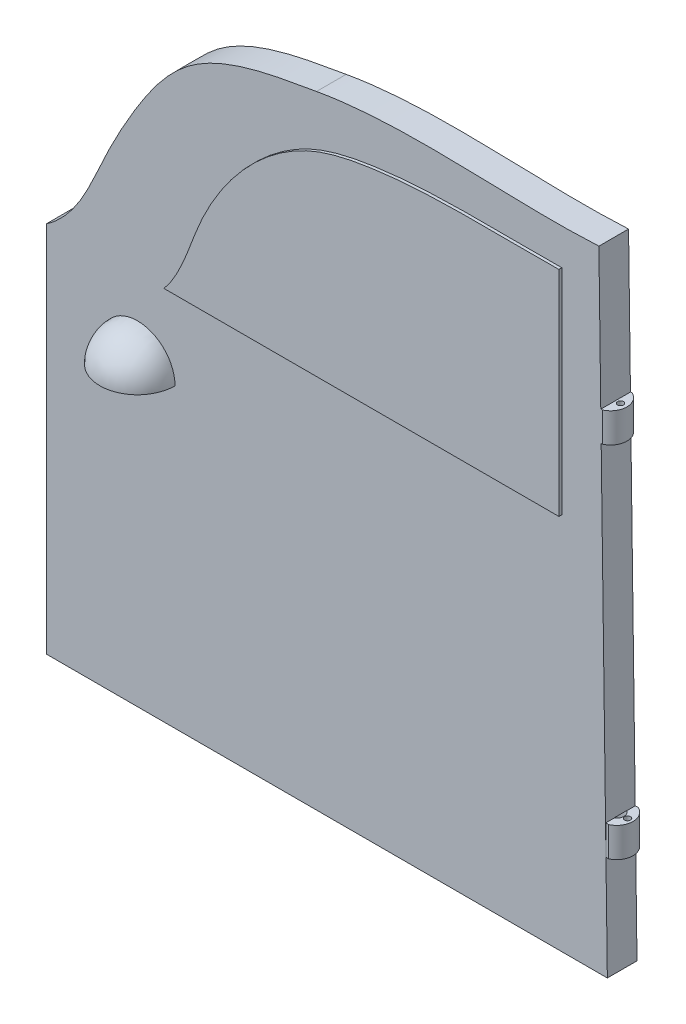
SolidWorks part; units mm, degrees
ref_plane "Front Plane" through (0, 0, 0) normal (0, 0, 1) x (1, 0, 0)
ref_plane "Top Plane" through (0, 0, 0) normal (0, 1, 0) x (1, 0, 0)
ref_plane "Right Plane" through (0, 0, 0) normal (1, 0, 0) x (0, 0, -1)
sketch "Sketch1" plane through (0, 0, 0) normal (0, 0, 1) x (1, 0, 0)
  line L0 (-221.4454, 149.8652) -> (535.2213, 149.8652) construction
  line L1 (186.2801, 212.2169) -> (189.1274, 0)
  line L2 (189.1274, 0) -> (0, 0)
  line L3 (0, 0) -> (0, 125.5767)
  spline S0 degree 3 poles (0, 125.5767) (10.557, 132.8376) (17.0982, 150.7511) (30.5385, 175.7634) (49.3522, 203.0408) (76.8679, 207.297) (91.098, 209.7763) knots 0 0 0 0 0.275246 0.426572 0.655829 1 1 1 1
  spline S1 degree 3 poles (91.098, 209.7763) (122.5651, 215.3748) (154.601, 210.5155) (186.2801, 212.2169) knots 0 0 0 0 1 1 1 1
sketch "Sketch2" plane through (0, 0, 0) normal (0, 0, 1) x (1, 0, 0)
extrude "Boss-Extrude1" add sketch "Sketch1" along normal blind 10
sketch "Sketch3" plane through (0, 0, 10) normal (0, 0, 1) x (1, 0, 0)
  line L0 (40.6919, 127.5652) -> (173.8037, 127.5652)
  line L1 (173.8037, 127.5652) -> (173.8037, 199.6793)
  spline S0 degree 3 poles (40.6919, 127.5652) (46.7713, 134.9333) (53.3691, 161.7045) (78.4575, 191.2123) (124.3175, 201.0388) (152.2649, 199.3628) (173.8037, 199.6793) knots 0 0 0 0 0.165618 0.500502 0.611599 1 1 1 1
extrude "Boss-Extrude2" add sketch "Sketch3" along normal blind 1 and the other way blind 11
sketch "Sketch4" plane through (0, 0, 10) normal (0, 0, 1) x (1, 0, 0)
  line L0 (18.099, 100.0012) -> (43.4131, 100.0012)
  line L1 (30.756, 100.0012) -> (30.756, 0) construction
  line L2 (0, 0) -> (189.1274, 0) construction
  line L3 (30.756, 100.0012) -> (187.7857, 100.0012) construction
  line L4 (189.1274, 0) -> (186.2801, 212.2169) construction
  arc A0 (18.099, 100.0012) -> (43.4131, 100.0012) centre (30.756, 100.0012) cw
  dimension "D1" = 100.0012
ref_plane "Plane1" through (0, 100, 0) normal (0, -1, 0) x (-1, 0, 0)
sketch "Sketch5" plane through (0, 100, 0) normal (0, -1, 0) x (-1, 0, 0)
  line L0 (-18.099, -10) -> (-43.4131, -10)
  line L1 (-18.099, -10) -> (-43.4131, -10) construction
  line L2 (0, -10) -> (-189.1274, -10) construction
  line L3 (-43.4131, -10) -> (-18.099, -10) construction
  arc A0 (-18.099, -10) -> (-43.4131, -10) centre (-30.756, -5.6887) cw
ref_plane "Plane2" through (32.1075, 0.4308, 0) normal (0.9999, 0.0134, 0) x (0, 0, -1)
sketch "Sketch6" plane through (32.1075, 0.4308, 0) normal (0.9999, 0.0134, 0) x (0, 0, -1)
  line L1 (-10, 112.2366) -> (-10, 99.4097) construction
  ellipse E3 centre (-5.6887, 99.5784) end of major axis (-19.0599, 99.5784) minor radius 0.1794 (-10, 99.7482) -> (-10, 99.4086) ccw construction
  spline S0 degree 3 poles (-19.0598, 99.5782) (-18.7168, 104.9477) (-15.4228, 110.6613) (-10, 112.2366) knots 0 0 0 0 1 1 1 1
revolve "Revolve1" add sketch "Sketch4" angle 90 about L0
sketch "Sketch7" plane through (0, 100.0012, 0) normal (0, -1, 0) x (1, 0, 0)
  line L0 (18.099, 10) -> (43.4131, 10) construction
  line L1 (19.7854, 10) -> (41.9159, 10) construction
  line L2 (19.7854, 10) -> (41.9159, 10)
  arc A0 (19.7854, 10) -> (41.9159, 10) centre (30.8507, 8.9637) cw
revolve "Cut-Revolve1" cut sketch "Sketch7" angle 45 about L1 other way angle 90
ref_plane "Plane3" through (0, 40, 0) normal (0, -1, 0) x (-1, 0, 0)
ref_plane "Plane4" through (0, 160, 0) normal (0, -1, 0) x (-1, 0, 0)
sketch "Sketch16" plane through (189.0934, 2.5371, 0) normal (0.9999, 0.0134, 0) x (0, 0, -1)
  line L0 (-10, 38.6394) -> (0, 38.6394) construction
  line L1 (-10, -2.5373) -> (-10, 209.6987) construction
  line L2 (0, -2.5373) -> (0, 209.6987) construction
  line L3 (-10, 158.0625) -> (0, 158.0625) construction
sketch "Sketch17" plane through (0, 40, 0) normal (0, -1, 0) x (-1, 0, 0)
  line L0 (-188.575, 0) -> (-189.575, 0)
  line L1 (-188.575, -10) -> (-188.575, 0) construction
  line L2 (-188.575, -9.9807) -> (-189.575, -9.9807)
  line L3 (-188.575, 0) -> (-188.575, -9.9807)
  arc A1 (-189.575, -9.9807) -> (-189.575, 0) centre (-187.2628, -4.9904) cw
  dimension "D1" = 1
extrude "Boss-Extrude3" add sketch "Sketch17" along normal blind 5 and the other way blind 5 contours L2 A1 L0 L3
sketch "Sketch18" plane through (0, 160, 0) normal (0, -1, 0) x (-1, 0, 0)
  line L0 (-186.9729, -10) -> (-187.4729, -10)
  line L1 (-186.9729, -10) -> (-186.9729, 0) construction
  line L2 (-186.9729, 0) -> (-187.4729, 0)
  line L3 (0, 0) -> (-189.1274, 0) construction
  line L4 (-188.6578, 0) -> (-189.575, 0) construction
  line L5 (-186.9729, 0) -> (-186.9729, -10)
  arc A1 (-187.4729, -10) -> (-187.4729, 0) centre (-185.2471, -5) cw
  dimension "D2" = 5.473
  dimension "D1" = 0.5
extrude "Boss-Extrude4" add sketch "Sketch18" along normal blind 5 and the other way blind 5 contours L2 A1 L0 L5
sketch "Sketch19" plane through (0, 155, 0) normal (0, -1, 0) x (1, 0, 0)
  line L0 (188.575, 10) -> (188.575, 0) construction
  circle A2 centre (188.575, 5) radius 1
extrude "Cut-Extrude3" cut sketch "Sketch19" against normal blind 10 contours A2
sketch "Sketch24" plane through (0, 35, 0) normal (0, -1, 0) x (1, 0, 0)
  circle A1 centre (190.9451, 4.9952) radius 1
extrude "Cut-Extrude4" cut sketch "Sketch24" against normal blind 10 contours A1
ref_plane "Plane11" through (0, 0, -150) normal (0, 0, -1) x (-1, 0, 0)
mirror "Mirror3" [suppressed] about plane through (0, 0, -150) normal (0, 0, -1)
ref_plane "Plane10" through (0, 45, 0) normal (0, 1, 0) x (1, 0, 0)
sketch "Sketch21" plane through (0, 45, 0) normal (0, 1, 0) x (1, 0, 0)
  circle A0 centre (187.2628, -4.9904) radius 2.5
extrude "Cut-Extrude2" cut sketch "Sketch21" against normal blind 10
